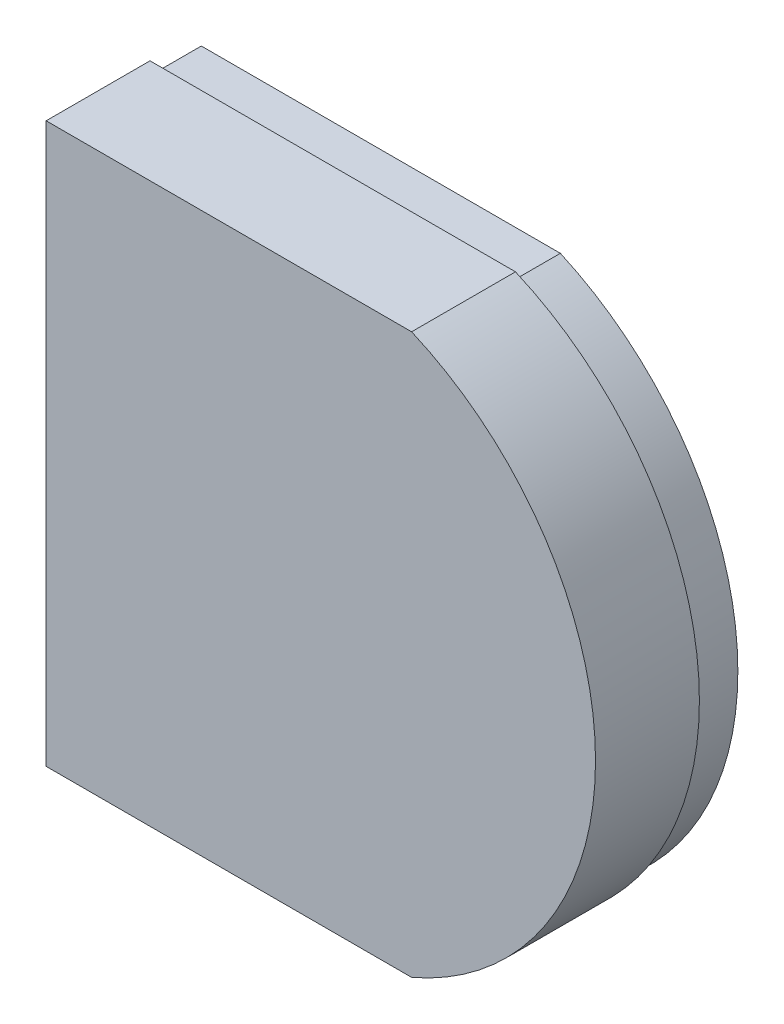
SolidWorks part; units mm, degrees
ref_plane "Front Plane" through (0, 0, 0) normal (0, 0, 1) x (1, 0, 0)
ref_plane "Top Plane" through (0, 0, 0) normal (0, 1, 0) x (1, 0, 0)
ref_plane "Right Plane" through (0, 0, 0) normal (1, 0, 0) x (0, 0, -1)
sketch "Sketch1" plane through (0, 0, 0) normal (0, 0, 1) x (1, 0, 0)
  line L1 (-74.2297, 45.7275) -> (-49.2297, 45.7275)
  line L2 (-74.2297, 45.7275) -> (-74.2297, 5.7275)
  line L3 (-74.2297, 5.7275) -> (-49.2297, 5.7275)
  line L4 (-49.2297, 45.7275) -> (-49.2297, 5.7275)
  dimension "D1" = 40
  dimension "D2" = 25
extrude "Boss-Extrude1" add sketch "Sketch1" along normal blind 8
sketch "Sketch2" plane through (0, 0, 0) normal (0, 0, 1) x (1, 0, 0)
  line L0 (-77.8888, 47.5275) -> (-77.8888, 3.9275)
  line L5 (-61.7297, 45.7275) -> (-61.7297, 25.7275)
  line L6 (-49.2297, 45.7275) -> (-74.2297, 45.7275) construction
  line L8 (-77.8888, 47.5275) -> (-49.3888, 47.5275)
  line L10 (-77.8888, 3.9275) -> (-49.3888, 3.9275)
  circle A1 centre (-42.3892, 25.7624) radius 48.5612
  arc A3 (-49.3888, 47.5275) -> (-49.3888, 3.9275) centre (-58.7867, 25.7275) cw
  dimension "D6" = 43.6
  dimension "D8" = 28.5
  dimension "D9" = 28.5
extrude "Boss-Extrude5" add sketch "Sketch2" along normal blind 10.6 and the other way blind 1 contours L8 L0 region at (-58.2685, 25.7275, 0)
sketch "Sketch8" plane through (0, 0, 0) normal (0, 0, 1) x (1, 0, 0)
  line L0 (-76.8888, 46.5275) -> (-76.8888, 4.9275)
  line L1 (-76.8888, 4.9275) -> (-49.3888, 4.9275)
  line L2 (-76.8888, 46.5275) -> (-49.3888, 46.5275)
  line L3 (-77.8888, 47.5275) -> (-77.8888, 3.9275) construction
  arc A0 (-49.3888, 4.9275) -> (-49.3888, 46.5275) centre (-58.9321, 25.7275) ccw
  arc A2 (-49.3888, 3.9275) -> (-49.3888, 47.5275) centre (-58.7867, 25.7275) ccw construction
  point P8 (-36.0473, 25.7275)
  point P12 (-35.0473, 25.7275)
  dimension "D1" = 1
  dimension "D2" = 1
  dimension "D3" = 1
  dimension "D4" = 1
extrude "Cut-Extrude2" cut sketch "Sketch8" against normal blind 6 and the other way blind 9 contours A0 L2 L0 L1
sketch "Sketch9" plane through (0, 0, 0) normal (0, 0, 1) x (1, 0, 0)
  line L0 (-37.7093, 30.2625) -> (-37.7093, 29.3916)
  line L1 (-37.7093, 22.0742) -> (-37.7093, 21.228)
  line L2 (-46.6022, 30.9745) -> (-46.6022, 30.0766)
  line L3 (-46.6022, 21.3784) -> (-46.6022, 20.6468)
  arc A3 (-37.7093, 30.2625) -> (-46.6022, 30.9745) centre (-42.5385, 25.8379) ccw
  arc A4 (-37.7093, 21.228) -> (-46.6022, 20.6468) centre (-42.4688, 25.7275) cw
  arc A5 (-37.7093, 29.3916) -> (-46.6022, 30.0766) centre (-42.4641, 25.732) ccw
  arc A6 (-37.7093, 22.0742) -> (-46.6022, 21.3784) centre (-42.4688, 25.7275) cw
sketch "Sketch11" plane through (0, 0, -1) normal (0, 0, -1) x (-1, 0, 0)
  line L0 (76.8888, 46.5275) -> (76.8888, 4.9275) construction
  line L1 (49.3888, 47.5275) -> (77.8888, 47.5275)
  line L2 (49.3888, 4.4275) -> (77.3888, 4.4275)
  line L3 (77.3888, 4.4275) -> (77.3888, 47.0275)
  line L4 (77.3888, 47.0275) -> (49.3888, 47.0275)
  line L5 (77.8888, 47.5275) -> (77.8888, 3.9275)
  line L6 (77.8888, 3.9275) -> (49.3888, 3.9275)
  arc A0 (49.3888, 47.0275) -> (49.3888, 4.4275) centre (58.8568, 25.7275) ccw
  arc A1 (49.3888, 47.5275) -> (49.3888, 3.9275) centre (58.7867, 25.7275) ccw construction
  arc A2 (49.3888, 47.5275) -> (49.3888, 3.9275) centre (58.7867, 25.7275) ccw
  point P16 (35.0473, 25.7275)
  point P17 (35.5473, 25.7275)
  dimension "D1" = 0.5
  dimension "D2" = 0.5
  dimension "D3" = 0.5
  dimension "D4" = 0.5
extrude "Cut-Extrude3" cut sketch "Sketch11" against normal blind 3.5
